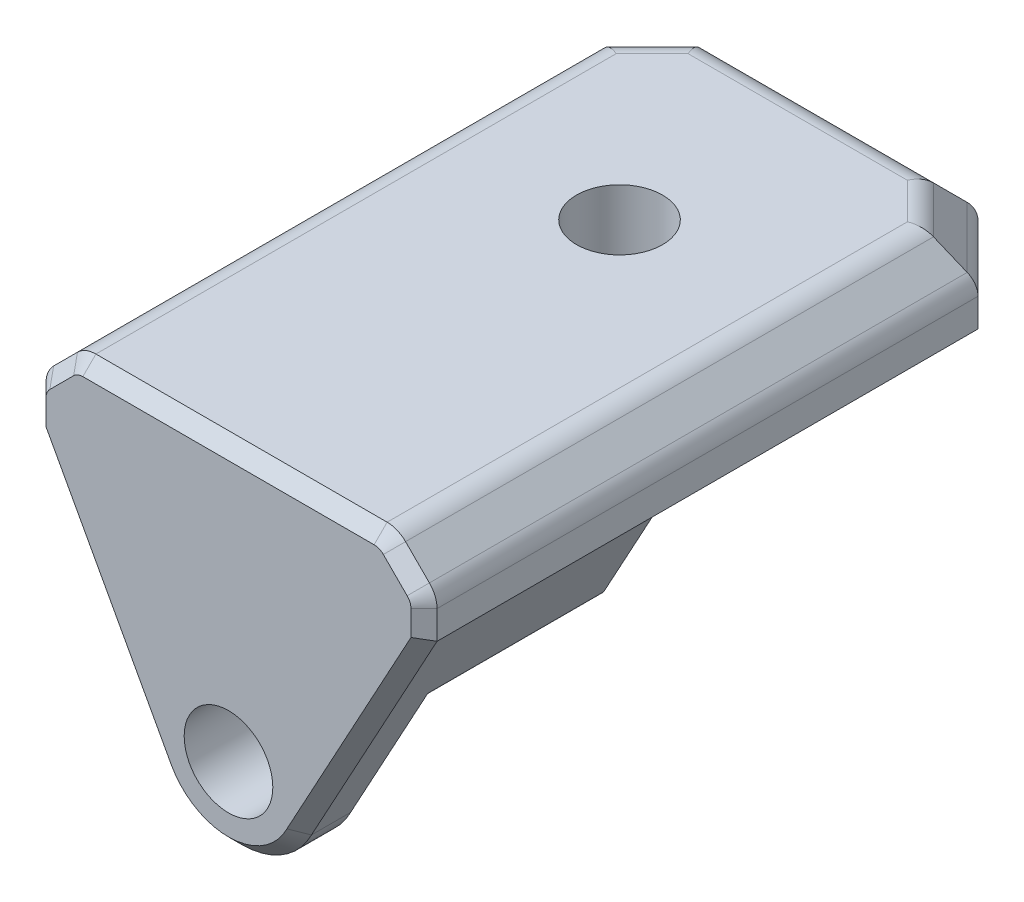
SolidWorks part; units mm, degrees
ref_plane "Front Plane" through (0, 0, 0) normal (0, 0, 1) x (1, 0, 0)
ref_plane "Top Plane" through (0, 0, 0) normal (0, 1, 0) x (1, 0, 0)
ref_plane "Right Plane" through (0, 0, 0) normal (1, 0, 0) x (0, 0, -1)
sketch "Sketch1" plane through (0, 0, 0) normal (0, 0, 1) x (1, 0, 0)
  line L0 (4.5962, 4.5962) -> (5.3033, 5.3033) construction
  line L1 (-4.5962, 4.5962) -> (-5.3033, 5.3033) construction
  line L2 (4.5962, 4.5962) -> (5.3033, 5.3033)
  line L3 (-4.5962, 4.5962) -> (-5.3033, 5.3033)
  line L4 (4.5941, 4.8769) -> (5.1619, 5.4447)
  line L5 (-4.5941, 4.8769) -> (-5.1619, 5.4447)
  line L6 (-4.5962, 4.5962) -> (-4.4548, 4.4548)
  line L8 (4.5962, 4.5962) -> (4.4548, 4.4548)
  circle A2 centre (0, 0) radius 7.5
  arc A4 (4.5941, 4.8769) -> (-4.5941, 4.8769) centre (0, 0) ccw
  circle A5 centre (0, 0) radius 6.3
  arc A7 (4.5962, 4.5962) -> (-4.5962, 4.5962) centre (0, 0) ccw construction
  dimension "D1" = 0.2
  dimension "D2" = 12.6
extrude "Boss-Extrude1" add sketch "Sketch1" against normal up to surface (2 mm away) contours A4 L4 A2 L5 region at (4.8017, 5.2352, 0)
extrude "Boss-Extrude2" add sketch "Sketch1<3>" along normal blind 4.75 contours A4 L4 A2 L5 region at (4.8017, 5.2352, 0)
sketch "Sketch1<3>" plane through (0, 0, 0) normal (0, 0, 1) x (1, 0, 0) same geometry as "Sketch1"
sketch "Sketch3" plane through (0, 0, 4.75) normal (0, 0, 1) x (1, 0, 0)
  line L0 (-5.16, 5.4428) -> (-2.821, -1.0208)
  line L1 (5.16, 5.4428) -> (2.821, -1.0208)
  line L2 (2.7807, 4.7453) -> (1.9028, 2.3194)
  line L3 (-2.7807, 4.7453) -> (-1.9028, 2.3194)
  line L4 (-2.7807, 4.7453) -> (-0.9403, -0.3403) construction
  line L5 (2.7807, 4.7453) -> (0.9403, -0.3403) construction
  circle A0 centre (0, 0) radius 3
  circle A1 centre (0, 0) radius 1.7 construction
  arc A2 (5.16, 5.4428) -> (-5.16, 5.4428) centre (0, 0) ccw construction
  arc A3 (5.16, 5.4428) -> (-5.16, 5.4428) centre (0, 0) ccw
  arc A4 (2.7807, 4.7453) -> (-2.7807, 4.7453) centre (0, 0) ccw
  circle A6 centre (0, 0) radius 1.7
  arc M3 (-4.5941, 4.8769) -> (4.5941, 4.8769) centre (0, 0) cw
  line M4 (4.5941, 4.8769) -> (5.16, 5.4428)
  arc M5 (5.16, 5.4428) -> (-5.16, 5.4428) centre (0, 0) ccw
  line M6 (-5.16, 5.4428) -> (-4.5941, 4.8769)
  dimension "D1" = 6
  dimension "D2" = 2
extrude "Boss-Extrude3" add sketch "Sketch3" along normal blind 2 contours A4 L2 A0 L1 L0 L3 M4 M3 M6 | M6 M3 M4 M5 | A0 A6 | L2 A4 L3 A0 region at (-4.9682, 5.0687, 4.75) region at (0, 7.3935, 4.75) region at (-2.8109, 0.7727, 4.75) region at (0, 4.0816, 4.75)
sketch "Sketch4" plane through (0, 0, 4.75) normal (0, 0, -1) x (-1, 0, 0)
  circle A2 centre (0, 0) radius 2.2
  circle A3 centre (0, 0) radius 2.2
  circle M6 centre (0, 0) radius 1.7
  dimension "D1" = 0.5
extrude "Boss-Extrude4" add sketch "Sketch4" along normal blind 0.5 contours A3 M6 region at (2.1378, 0, 4.75)
chamfer "Chamfer1" distance 0.5 angle 45 1 edges at (2.2, 0, 4.75)
sketch "Sketch5" plane through (0, 0, 6.75) normal (0, 0, 1) x (1, 0, 0)
  line L0 (0, 10.5) -> (0, 7.5) construction
  line L1 (-7.5, 10.5) -> (7.5, 10.5)
  line L2 (-7.5, 10.5) -> (-7.5, 7.5)
  line L3 (-7.5, 7.5) -> (7.5, 7.5)
  line L4 (7.5, 10.5) -> (7.5, 7.5)
  line L5 (-7.5, 7.5) -> (-2.6347, -1.4347)
  line L6 (7.5, 7.5) -> (2.5835, -1.525)
  arc A0 (-2.821, -1.0208) -> (2.821, -1.0208) centre (0, 0) ccw construction
  arc A1 (5.16, 5.4428) -> (-5.16, 5.4428) centre (0, 0) ccw construction
  arc A2 (-2.821, -1.0208) -> (2.821, -1.0208) centre (0, 0) ccw
  line M12 (2.821, -1.0208) -> (5.16, 5.4428)
  arc M13 (5.16, 5.4428) -> (-5.16, 5.4428) centre (0, 0) ccw
  line M14 (-5.16, 5.4428) -> (-2.821, -1.0208)
  arc M15 (-2.821, -1.0208) -> (2.821, -1.0208) centre (0, 0) ccw
  dimension "D1" = 15
  dimension "D2" = 3
extrude "Boss-Extrude5" add sketch "Sketch5" against normal up to surface (2 mm away) contours L3 L5 M15 M14 M13 | L0 L1 L2 L3 | L1 L0 L3 L4 | L6 L3 M13 M12 M15 region at (3.75, 9, 6.75) region at (-3.75, 9, 6.75) region at (-2.8207, 7.0751, 6.75) region at (3.75, 7.384, 6.75) up to face at (2.7, 0, 4.75)
sketch "Sketch6" plane through (0, 0, 4.75) normal (0, 0, -1) x (-1, 0, 0)
  line L0 (-2.6823, -1.3436) -> (-7.5, 7.5)
  line L1 (2.6347, -1.4347) -> (7.5, 7.5)
  arc A0 (5.4997, 3.8266) -> (-5.4992, 3.8273) centre (0, 0) ccw
  arc A1 (5.922, 4.6022) -> (-5.9216, 4.6027) centre (0, 0) ccw
  line M9 (-4.5941, 4.8769) -> (-5.16, 5.4428)
  line M11 (5.16, 5.4428) -> (4.5941, 4.8769)
extrude "Boss-Extrude6" add sketch "Sketch6" along normal up to surface (6.75 mm away) contours A1 L0 A0 M9 | L1 A1 A0 M11 region at (5.3001, 4.6896, 4.75) region at (-5.3003, 4.6893, 4.75) up to face at (0, 6.1299, -2)
sketch "Sketch8" plane through (0, 0, 4.75) normal (0, 0, -1) x (-1, 0, 0)
  line L5 (5.922, 4.6022) -> (7.5, 7.5)
  line L6 (7.5, 7.5) -> (7.5, 10.5)
  line L7 (7.5, 10.5) -> (-7.5, 10.5)
  line L8 (-7.5, 10.5) -> (-7.5, 7.5)
  line L9 (-7.5, 7.5) -> (-5.9216, 4.6027)
  line L10 (5.922, 4.6022) -> (7.5, 7.5)
  line L11 (7.5, 7.5) -> (7.5, 10.5)
  line L12 (7.5, 10.5) -> (-7.5, 10.5)
  line L13 (-7.5, 10.5) -> (-7.5, 7.5)
  line L14 (-7.5, 7.5) -> (-5.9216, 4.6027)
  arc A1 (5.922, 4.6022) -> (-5.9216, 4.6027) centre (0, 0) ccw
  arc A2 (5.922, 4.6022) -> (-5.9216, 4.6027) centre (0, 0) ccw
  dimension "D1" = 0
extrude "Boss-Extrude8" add sketch "Sketch8" along normal up to surface (6.75 mm away) up to face at (-0.0003, 5.6573, -2)
sketch "Sketch10" plane through (0, 0, -2) normal (0, 0, -1) x (-1, 0, 0)
  line L1 (-7.5, 10.5) -> (7.5, 10.5)
  line L2 (-7.5, 10.5) -> (-7.5, 7.5)
  line L3 (-7.5, 7.5) -> (7.5, 7.5)
  line L4 (7.5, 10.5) -> (7.5, 7.5)
extrude "Boss-Extrude9" add sketch "Sketch10" along normal blind 15
chamfer "Chamfer5" distance 2.5 angle 45 2 edges at (-7.5, 9, -17) (7.5, 9, -17)
sketch "Sketch11" plane through (0, 7.5, 0) normal (0, -1, 0) x (1, 0, 0)
  line L0 (7.5, -8.25) -> (-7.5, -8.25) construction
  line L1 (7.5, -14.5) -> (7.5, -2) construction
  line L2 (-7.5, -14.5) -> (-7.5, -2) construction
  line L3 (0, -17) -> (0, -8.25) construction
  line L4 (5, -17) -> (-5, -17) construction
  circle A0 centre (0, -8.25) radius 1.65
  dimension "D1" = 3.3
extrude "Cut-Extrude1" cut sketch "Sketch11" against normal through all
fillet "Fillet1" radius 0.2 2 edges at (-5.4997, 3.8266, 1.375) (5.4992, 3.8273, 1.375)
chamfer "Chamfer6" distance 1.5 angle 45 5 edges at (-7.5, 10.5, -3.875) (-6.25, 10.5, -15.75) (0, 10.5, -17) (6.25, 10.5, -15.75) (7.5, 10.5, -3.875)
fillet "Fillet3" radius 1 10 edges at (6, 10.5, -3.5643) (7.5, 9, -3.875) (5.1893, 10.5, -14.6893) (6.25, 9, -15.75) (0, 9, -17) (0, 10.5, -15.5) (-5.1893, 10.5, -14.6893) (-6.25, 9, -15.75) (-7.5, 9, -3.875) (-6, 10.5, -3.5643)
chamfer "Chamfer7" distance 0.5 angle 45 12 edges at (0.0514, -2.9996, 6.75) (-5.0673, 3.0327, 6.75) (6.75, 9.75, 6.75) (-7.5, 8.0429, 6.75) (7.5, 8.0429, 6.75) (-7.4239, 8.9685, 6.75) (7.4239, 8.9685, 6.75) (-6.75, 9.75, 6.75) (-5.9685, 10.4239, 6.75) (5.9685, 10.4239, 6.75) (0, 10.5, 6.75) (5.0912, 3.0782, 6.75)
sketch "Sketch12" plane through (0, 0, -2) normal (0, 0, -1) x (-1, 0, 0)
  line L0 (-5.6501, 4.1043) -> (-5.2835, 3.4314)
  line L1 (5.6506, 4.1037) -> (5.284, 3.4306)
  line L7 (5.6506, 4.1037) -> (7.5, 7.5)
  line L8 (7.5, 7.5) -> (-7.5, 7.5)
  line L9 (-7.5, 7.5) -> (-5.6501, 4.1043)
  line L14 (5.6506, 4.1037) -> (7.5, 7.5)
  line L15 (7.5, 7.5) -> (-7.5, 7.5)
  line L16 (-7.5, 7.5) -> (-5.6501, 4.1043)
  arc A0 (5.284, 3.4306) -> (-5.2835, 3.4314) centre (0, 0) ccw
  arc A1 (5.853, 4.4755) -> (-5.8526, 4.476) centre (0, 0) ccw
  arc A9 (5.3163, 4.0777) -> (-5.3158, 4.0782) centre (0, 0) ccw
  arc A10 (5.3163, 4.0777) -> (5.6506, 4.1037) centre (5.475, 4.1994) ccw
  arc A11 (-5.6501, 4.1043) -> (-5.3158, 4.0782) centre (-5.4745, 4.2) ccw
  arc A16 (5.3163, 4.0777) -> (-5.3158, 4.0782) centre (0, 0) ccw
  arc A17 (5.3163, 4.0777) -> (5.6506, 4.1037) centre (5.475, 4.1994) ccw
  arc A18 (-5.6501, 4.1043) -> (-5.3158, 4.0782) centre (-5.4745, 4.2) ccw
  dimension "D1" = 12.6
  dimension "D2" = 0
